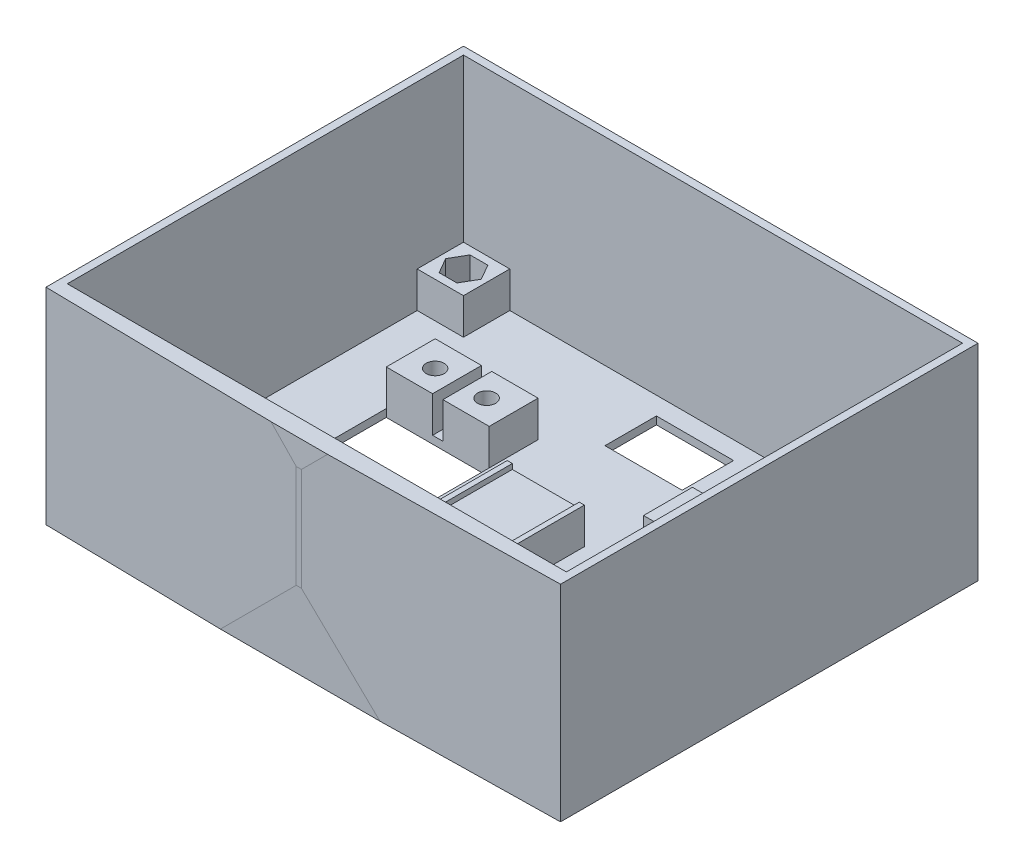
SolidWorks part; units mm, degrees
ref_plane "Plan de face" through (0, 0, 0) normal (0, 0, 1) x (1, 0, 0)
ref_plane "Plan de dessus" through (0, 0, 0) normal (0, 1, 0) x (1, 0, 0)
ref_plane "Plan de droite" through (0, 0, 0) normal (1, 0, 0) x (0, 0, -1)
sketch "Esquisse1" plane through (0, 0, 0) normal (0, 1, 0) x (1, 0, 0)
  line L1 (0, 0) -> (100, 0)
  line L2 (0, 0) -> (0, 80)
  line L3 (0, 80) -> (100, 80)
  line L4 (100, 0) -> (100, 80)
  line L5 (15, 50) -> (35, 50)
  line L6 (15, 50) -> (15, 11)
  line L7 (15, 11) -> (35, 11)
  line L8 (35, 50) -> (35, 11)
  line L9 (65, 50) -> (85, 50)
  line L10 (65, 50) -> (65, 11)
  line L11 (65, 11) -> (85, 11)
  line L12 (85, 50) -> (85, 11)
  line L13 (42.5, 75) -> (57.5, 75)
  line L14 (42.5, 75) -> (42.5, 65)
  line L15 (42.5, 65) -> (57.5, 65)
  line L16 (57.5, 75) -> (57.5, 65)
  dimension "D1" = 80
  dimension "D2" = 100
  dimension "D3" = 20
  dimension "D4" = 39
  dimension "D5" = 20
  dimension "D6" = 39
  dimension "D7" = 15
  dimension "D8" = 15
  dimension "D9" = 30
  dimension "D10" = 30
  dimension "D11" = 15
  dimension "D12" = 10
  dimension "D13" = 42.5
  dimension "D14" = 5
extrude "Boss.-Extru.2" add sketch "Esquisse1" along normal blind 1.5
sketch "Esquisse2" plane through (0, 1.5, 0) normal (0, 1, 0) x (1, 0, 0)
  line L1 (0, 80) -> (100, 80)
  line L2 (0, 80) -> (0, 0)
  line L3 (0, 0) -> (100, 0)
  line L4 (100, 80) -> (100, 0)
  line L5 (1.5, 78.5) -> (98.5, 78.5)
  line L6 (1.5, 78.5) -> (1.5, 1.5)
  line L7 (1.5, 1.5) -> (98.5, 1.5)
  line L8 (98.5, 78.5) -> (98.5, 1.5)
  dimension "D1" = 1.5
  dimension "D2" = 1.5
  dimension "D3" = 1.5
  dimension "D4" = 1.5
extrude "Boss.-Extru.3" add sketch "Esquisse2" along normal blind 38.5
sketch "Esquisse3" plane through (0, 1.5, 0) normal (0, 1, 0) x (1, 0, 0)
  line L0 (1.5, 1.5) -> (98.5, 1.5) construction
  line L1 (15, 50) -> (24, 50)
  line L2 (15, 50) -> (15, 59.5)
  line L3 (15, 59.5) -> (24, 59.5)
  line L4 (24, 50) -> (24, 59.5)
  line L5 (26, 59.5) -> (35, 59.5)
  line L6 (26, 59.5) -> (26, 50)
  line L7 (26, 50) -> (35, 50)
  line L8 (35, 59.5) -> (35, 50)
  line L9 (15, 11) -> (24, 11)
  line L10 (15, 11) -> (15, 1.5)
  line L11 (15, 1.5) -> (24, 1.5)
  line L12 (24, 11) -> (24, 1.5)
  line L13 (65, 50) -> (74, 50)
  line L14 (35, 11) -> (26, 11)
  line L15 (35, 11) -> (35, 1.5)
  line L16 (35, 1.5) -> (26, 1.5)
  line L17 (26, 11) -> (26, 1.5)
  line L18 (65, 50) -> (65, 59.5)
  line L19 (65, 59.5) -> (74, 59.5)
  line L20 (74, 50) -> (74, 59.5)
  line L21 (76, 59.5) -> (85, 59.5)
  line L22 (76, 59.5) -> (76, 50)
  line L23 (76, 50) -> (85, 50)
  line L24 (85, 59.5) -> (85, 50)
  line L25 (64.7387, 11) -> (74, 11)
  line L26 (64.7387, 11) -> (64.7387, 1.5)
  line L27 (64.7387, 1.5) -> (74, 1.5)
  line L28 (74, 11) -> (74, 1.5)
  line L29 (85, 11) -> (76, 11)
  line L30 (85, 11) -> (85, 1.5)
  line L31 (85, 1.5) -> (76, 1.5)
  line L32 (76, 11) -> (76, 1.5)
  line L35 (85, 50) -> (65, 50) construction
  line L36 (65, 11) -> (85, 11) construction
  line L37 (85, 11) -> (85, 50) construction
  line L38 (98.5, 1.5) -> (98.5, 78.5) construction
  line L39 (42.5, 46) -> (57.5, 46)
  line L40 (42.5, 46) -> (42.5, 29)
  line L41 (42.5, 29) -> (57.5, 29)
  line L42 (57.5, 46) -> (57.5, 29)
  line L44 (98.5, 78.5) -> (1.5, 78.5) construction
  line L45 (1.5, 78.5) -> (10.5, 78.5)
  line L46 (1.5, 78.5) -> (1.5, 69.5)
  line L47 (1.5, 69.5) -> (10.5, 69.5)
  line L48 (10.5, 78.5) -> (10.5, 69.5)
  line L49 (1.5, 78.5) -> (1.5, 1.5) construction
  line L51 (98.5, 78.5) -> (89.5, 78.5)
  line L52 (98.5, 78.5) -> (98.5, 69.5)
  line L53 (98.5, 69.5) -> (89.5, 69.5)
  line L54 (89.5, 78.5) -> (89.5, 69.5)
  line L55 (98.5, 1.5) -> (89.5, 1.5)
  line L56 (98.5, 1.5) -> (98.5, 10.5)
  line L57 (98.5, 10.5) -> (89.5, 10.5)
  line L58 (89.5, 1.5) -> (89.5, 10.5)
  line L59 (1.5, 1.5) -> (10.5, 1.5)
  line L60 (1.5, 1.5) -> (1.5, 10.5)
  line L61 (1.5, 10.5) -> (10.5, 10.5)
  line L62 (10.5, 1.5) -> (10.5, 10.5)
  dimension "D1" = 2
  dimension "D2" = 9
  dimension "D3" = 9.5
  dimension "D4" = 9.5
  dimension "D5" = 2
  dimension "D6" = 9
  dimension "D7" = 2
  dimension "D8" = 9
  dimension "D9" = 9.5
  dimension "D10" = 9.5
  dimension "D11" = 2
  dimension "D12" = 9
  dimension "D13" = 17
  dimension "D14" = 15
  dimension "D15" = 27.5
  dimension "D16" = 41
  dimension "D17" = 9
  dimension "D18" = 9
  dimension "D19" = 9
  dimension "D20" = 9
  dimension "D21" = 9
  dimension "D22" = 9
  dimension "D23" = 9
  dimension "D24" = 9
extrude "Boss.-Extru.4" add sketch "Esquisse3" along normal blind 7
sketch "Esquisse4" plane through (0, 8.5, 0) normal (0, 1, 0) x (1, 0, 0)
  line L1 (15, 59.5) -> (15, 50) construction
  line L4 (24, 11) -> (15, 11) construction
  line L5 (15, 11) -> (15, 1.5) construction
  line L6 (35, 1.5) -> (35, 11) construction
  line L7 (35, 11) -> (26, 11) construction
  line L8 (74, 11) -> (64.7387, 11) construction
  line L9 (64.7387, 11) -> (64.7387, 1.5) construction
  line L10 (85, 11) -> (76, 11) construction
  line L11 (76, 11) -> (76, 1.5) construction
  line L12 (85, 50) -> (85, 59.5) construction
  line L13 (74, 50) -> (74, 59.5) construction
  line L14 (65, 50) -> (74, 50) construction
  line L15 (76, 50) -> (85, 50) construction
  line L16 (42.5, 29) -> (57.5, 29) construction
  line L17 (57.5, 29) -> (57.5, 46) construction
  line L18 (15, 50) -> (24, 50) construction
  line L19 (10.5, 69.5) -> (10.5, 78.5) construction
  line L20 (1.5, 69.5) -> (10.5, 69.5) construction
  line L21 (10.5, 1.5) -> (10.5, 10.5) construction
  line L22 (10.5, 10.5) -> (1.5, 10.5) construction
  line L23 (98.5, 10.5) -> (89.5, 10.5) construction
  line L24 (89.5, 10.5) -> (89.5, 1.5) construction
  line L25 (26, 50) -> (35, 50) construction
  line L26 (89.5, 69.5) -> (98.5, 69.5) construction
  line L27 (89.5, 78.5) -> (89.5, 69.5) construction
  line L28 (35, 50) -> (35, 59.5) construction
  circle A0 centre (20, 54.5) radius 1.75
  circle A1 centre (30, 54.5) radius 1.75
  circle A2 centre (30, 6.5) radius 1.75
  circle A3 centre (20, 6.5) radius 1.75
  circle A4 centre (69.7387, 6.5) radius 1.75
  circle A5 centre (80, 6.5) radius 1.75
  circle A6 centre (70, 54.5) radius 1.75
  circle A7 centre (80, 54.5) radius 1.75
  circle A8 centre (54, 32.5) radius 1.25
  circle A9 centre (6, 74) radius 1.75
  circle A10 centre (6, 6) radius 1.75
  circle A11 centre (94, 6) radius 1.75
  circle A12 centre (94, 74) radius 1.75
  dimension "D1" = 3.5
  dimension "D2" = 3.5
  dimension "D3" = 3.5
  dimension "D4" = 3.5
  dimension "D5" = 3.5
  dimension "D6" = 3.5
  dimension "D7" = 3.5
  dimension "D8" = 3.5
  dimension "D9" = 4.5
  dimension "D10" = 5
  dimension "D11" = 4.5
  dimension "D12" = 5
  dimension "D13" = 4.5
  dimension "D14" = 5
  dimension "D15" = 5
  dimension "D16" = 4.5
  dimension "D17" = 4.5
  dimension "D18" = 5
  dimension "D19" = 4.5
  dimension "D20" = 4
  dimension "D21" = 5
  dimension "D22" = 4
  dimension "D23" = 4.5
  dimension "D24" = 4.5
  dimension "D25" = 2.5
  dimension "D26" = 3.5
  dimension "D27" = 3.5
  dimension "D28" = 3.5
  dimension "D29" = 4.5
  dimension "D30" = 4.5
  dimension "D31" = 3.5
  dimension "D32" = 4.5
  dimension "D33" = 4.5
  dimension "D34" = 3.5
  dimension "D35" = 4.5
  dimension "D36" = 4.5
  dimension "D37" = 3.5
  dimension "D38" = 4.5
  dimension "D39" = 4.5
extrude "Enlèv. mat.-Extru.1" cut sketch "Esquisse4" against normal blind 15
sketch "Esquisse6" plane through (0, 1.5, 0) normal (0, 1, 0) x (1, 0, 0)
  text T0 "Y→\r\n"
  text T1 "X\r\n↓\r\n\r\n"
extrude "Boss.-Extru.5" add sketch "Esquisse6" along normal blind 0.5
sketch "Esquisse7" plane through (0, 8.5, 0) normal (0, 1, 0) x (1, 0, 0)
  line L1 (43.5, 46) -> (56.5, 46)
  line L2 (43.5, 46) -> (43.5, 30)
  line L3 (43.5, 30) -> (56.5, 30)
  line L4 (56.5, 46) -> (56.5, 30)
  line L5 (57.5, 29) -> (57.5, 46) construction
  line L6 (42.5, 29) -> (57.5, 29) construction
  line L7 (42.5, 46) -> (42.5, 29) construction
  line L8 (57.5, 46) -> (42.5, 46) construction
  dimension "D2" = 1
  dimension "D3" = 1
  dimension "D4" = 1
extrude "Enlèv. mat.-Extru.2" cut sketch "Esquisse7" against normal blind 1
sketch "Esquisse8" plane through (0, 8.5, 0) normal (0, 1, 0) x (1, 0, 0)
  line L0 (10.5, 1.5) -> (10.5, 10.5) construction
  line L1 (7.3821, 3) -> (9.1141, 6)
  line L2 (9.1141, 6) -> (7.3821, 9)
  line L3 (7.3821, 9) -> (3.9179, 9)
  line L4 (3.9179, 9) -> (2.1859, 6)
  line L5 (2.1859, 6) -> (3.9179, 3)
  line L6 (3.9179, 3) -> (7.3821, 3)
  line L7 (10.5, 10.5) -> (1.5, 10.5) construction
  line L8 (10.5, 69.5) -> (10.5, 78.5) construction
  line L9 (7.7321, 71) -> (9.4641, 74)
  line L10 (9.4641, 74) -> (7.7321, 77)
  line L11 (7.7321, 77) -> (4.2679, 77)
  line L12 (4.2679, 77) -> (2.5359, 74)
  line L13 (2.5359, 74) -> (4.2679, 71)
  line L14 (4.2679, 71) -> (7.7321, 71)
  line L15 (1.5, 69.5) -> (10.5, 69.5) construction
  line L16 (89.5, 69.5) -> (98.5, 69.5) construction
  line L17 (97.4641, 74) -> (95.7321, 77)
  line L18 (95.7321, 77) -> (92.2679, 77)
  line L19 (92.2679, 77) -> (90.5359, 74)
  line L20 (90.5359, 74) -> (92.2679, 71)
  line L21 (92.2679, 71) -> (95.7321, 71)
  line L22 (95.7321, 71) -> (97.4641, 74)
  line L23 (89.5, 78.5) -> (89.5, 69.5) construction
  line L24 (98.5, 10.5) -> (89.5, 10.5) construction
  line L25 (95.7321, 3) -> (97.4641, 6)
  line L26 (97.4641, 6) -> (95.7321, 9)
  line L27 (95.7321, 9) -> (92.2679, 9)
  line L28 (92.2679, 9) -> (90.5359, 6)
  line L29 (90.5359, 6) -> (92.2679, 3)
  line L30 (92.2679, 3) -> (95.7321, 3)
  line L31 (89.5, 10.5) -> (89.5, 1.5) construction
  circle A0 centre (5.65, 6) radius 3 construction
  circle A1 centre (6, 74) radius 3 construction
  circle A2 centre (94, 74) radius 3 construction
  circle A3 centre (94, 6) radius 3 construction
  dimension "D10" = 6
  dimension "D1" = 6
  dimension "D2" = 4.85
  dimension "D3" = 4.5
  dimension "D4" = 6
  dimension "D5" = 4.5
  dimension "D6" = 4.5
  dimension "D7" = 6
  dimension "D8" = 4.5
  dimension "D9" = 4.5
  dimension "D11" = 4.5
  dimension "D12" = 4.5
extrude "Enlèv. mat.-Extru.3" cut sketch "Esquisse8" against normal blind 7
sketch "Esquisse9" plane through (0, 0, 0) normal (0, 0, 1) x (1, 0, 0)
  line L1 (49.5, 35) -> (50.5, 35)
  line L2 (49.5, 35) -> (49.5, 15)
  line L3 (49.5, 15) -> (50.5, 15)
  line L4 (50.5, 35) -> (50.5, 15)
  line L6 (100, 40) -> (100, 0) construction
  line L7 (0, 40) -> (100, 40) construction
  dimension "D1" = 1
  dimension "D2" = 49.5
  dimension "D3" = 5
extrude "Boss.-Extru.6" add sketch "Esquisse9" along normal blind 2
chamfer "Chanfrein1" distance 2 angle 89 4 edges at (50, 15, 0) (50.5, 25, 0) (50, 35, 0) (49.5, 25, 0) first distance on face at (50, 15, 1) first distance on face at (50.5, 25, 1) first distance on face at (50, 35, 1) first distance on face at (49.5, 25, 1)
